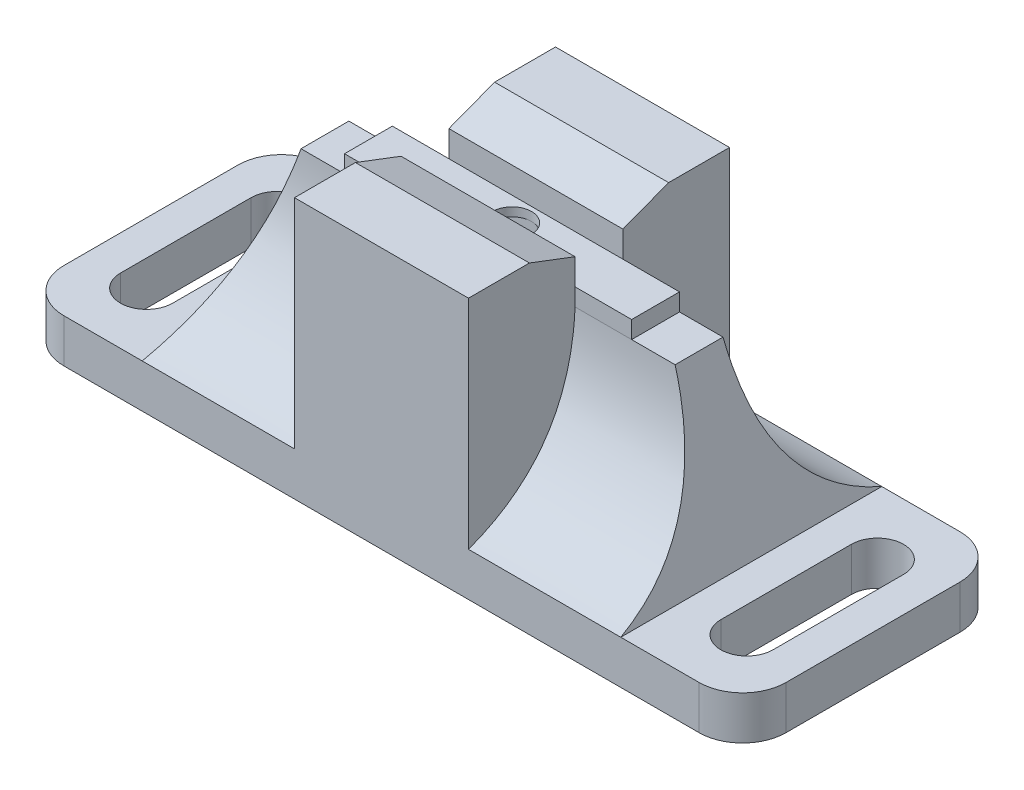
SolidWorks part; units mm, degrees
ref_plane "Front Plane" through (0, 0, 0) normal (0, 0, 1) x (1, 0, 0)
ref_plane "Top Plane" through (0, 0, 0) normal (0, 1, 0) x (1, 0, 0)
ref_plane "Right Plane" through (0, 0, 0) normal (1, 0, 0) x (0, 0, -1)
sketch "Sketch1" plane through (0, 0, 0) normal (0, 1, 0) x (1, 0, 0)
  line L0 (-34.5, 7.5) -> (-34.5, -7.5) construction
  line L1 (-36.5, 15) -> (36.5, 15)
  line L2 (-41.5, 10) -> (-41.5, -10)
  line L3 (-36.5, -15) -> (36.5, -15)
  line L4 (41.5, 10) -> (41.5, -10)
  line L5 (0, -15) -> (0, 15) construction
  line L6 (-41.5, 0) -> (41.5, 0) construction
  line L7 (-31.5, 7.5) -> (-31.5, -7.5)
  line L8 (-37.5, 7.5) -> (-37.5, -7.5)
  line L9 (34.5, 7.5) -> (34.5, -7.5) construction
  line L10 (31.5, 7.5) -> (31.5, -7.5)
  line L11 (37.5, 7.5) -> (37.5, -7.5)
  arc A0 (36.5, 15) -> (41.5, 10) centre (36.5, 10) cw
  arc A1 (36.5, -15) -> (41.5, -10) centre (36.5, -10) ccw
  arc A2 (-41.5, -10) -> (-36.5, -15) centre (-36.5, -10) ccw
  arc A3 (-36.5, 15) -> (-41.5, 10) centre (-36.5, 10) ccw
  arc A4 (-31.5, 7.5) -> (-37.5, 7.5) centre (-34.5, 7.5) ccw
  arc A5 (-37.5, -7.5) -> (-31.5, -7.5) centre (-34.5, -7.5) ccw
  arc A6 (31.5, 7.5) -> (37.5, 7.5) centre (34.5, 7.5) cw
  arc A7 (37.5, -7.5) -> (31.5, -7.5) centre (34.5, -7.5) cw
  point P0 (0, 0)
  point P6 (41.5, 15)
  point P14 (-41.5, -15)
  point P17 (-41.5, 15)
  point P20 (-34.5, 0)
  point P25 (0, 0)
  point P28 (34.5, 0)
  dimension "D3" = 5
  dimension "D1" = 30
  dimension "D2" = 83
  dimension "D4" = 6
  dimension "D5" = 4
  dimension "D6" = 15
extrude "Boss-Extrude1" add sketch "Sketch1" against normal blind 5
sketch "Sketch2" plane through (0, 0, 0) normal (1, 0, 0) x (0, 0, -1)
  line L0 (0, 0) -> (0, 18) construction
  line L1 (-2.75, 18) -> (2.75, 18)
  line L2 (-15, 0) -> (-15, 25)
  line L3 (-15, 25) -> (-8, 25)
  line L5 (-2.75, 18) -> (-2.75, 23)
  line L6 (-2.75, 23) -> (-8, 25)
  line L7 (2.75, 18) -> (2.75, 23)
  line L8 (2.75, 23) -> (8, 25)
  line L9 (15, 25) -> (8, 25)
  line L10 (15, 0) -> (15, 25)
  line L11 (-15, 0) -> (15, 0)
  spline S0 degree 2 poles (-15, 0) (-3.3423, 4.2875) (-2.75, 18) knots 0 0 0 1 1 1
  spline S1 degree 2 poles (15, 0) (3.3423, 4.2875) (2.75, 18) knots 0 0 0 1 1 1
  point P5 (0, 18)
  dimension "D1" = 18
  dimension "D2" = 5.5
  dimension "D3" = 25
  dimension "D4" = 5
  dimension "D5" = 7
extrude "Boss-Extrude2" add sketch "Sketch2" along normal mid plane 55 contours L11 L0 L1 S0 | L0 L11 S1 L1 region at (0, 6.3784, 3.8586) region at (0, 6.3784, -3.8586)
extrude "Boss-Extrude3" add sketch "Sketch2<3>" along normal mid plane 20 contours L2 S0 L5 L6 L3 | S1 L10 L9 L8 L7 region at (0, 14.2334, 9.6564) region at (0, 14.2334, -9.6564)
sketch "Sketch2<3>" plane through (0, 0, 0) normal (1, 0, 0) x (0, 0, -1) same geometry as "Sketch2"
sketch "Sketch5" plane through (0, 0, 0) normal (0, 0, 1) x (1, 0, 0)
  line L0 (10, 0) -> (10, 18) construction
  line L1 (27.5, 0) -> (27.5, 18) construction
  line L2 (27.5, 18) -> (10, 18) construction
  line L3 (-27.5, 0) -> (-36.5, 0) construction
  line L4 (-36.5, 0) -> (-36.5, -5) construction
  line L5 (-36.5, -5) -> (36.5, -5) construction
  line L6 (36.5, -5) -> (36.5, 0) construction
  line L7 (36.5, 0) -> (27.5, 0) construction
  line L8 (10, 0) -> (10, 25) construction
  line L9 (10, 25) -> (-10, 25) construction
  line L10 (-10, 25) -> (-10, 0) construction
  line L11 (-10, 18) -> (-10, 0) construction
  line L12 (-10, 18) -> (-27.5, 18) construction
  line L13 (-27.5, 18) -> (-27.5, 0) construction
  line L14 (10, 0) -> (10, 18)
  line L15 (27.5, 0) -> (27.5, 18)
  line L16 (27.5, 18) -> (10, 18)
  line L17 (-27.5, 0) -> (-36.5, 0)
  line L18 (-36.5, 0) -> (-36.5, -5)
  line L19 (-36.5, -5) -> (36.5, -5)
  line L20 (36.5, -5) -> (36.5, 0)
  line L21 (36.5, 0) -> (27.5, 0)
  line L22 (10, 0) -> (10, 25)
  line L23 (10, 25) -> (-10, 25)
  line L24 (-10, 25) -> (-10, 0)
  line L25 (-10, 18) -> (-10, 0)
  line L26 (-10, 18) -> (-27.5, 18)
  line L27 (-27.5, 18) -> (-27.5, 0)
  line L28 (-27.5, 0) -> (-21.5, 18)
  line L29 (27.5, 0) -> (21.5, 18)
  line L30 (-21.5, 18) -> (21.5, 18)
  line L31 (0, 0) -> (0, 18) construction
  line L32 (-21.5, 18) -> (-16.5, 18)
  line L33 (-21.5, 18) -> (-21.5, 16)
  line L34 (-21.5, 16) -> (-16.5, 16)
  line L35 (-16.5, 18) -> (-16.5, 16)
  line L36 (21.5, 18) -> (21.5, 16)
  line L37 (21.5, 16) -> (16.5, 16)
  line L38 (16.5, 18) -> (16.5, 16)
  line L40 (-16.5, 18) -> (16.5, 18)
  line L41 (-16.5, 18) -> (-16.5, 20)
  line L42 (-16.5, 20) -> (16.5, 20)
  line L43 (16.5, 18) -> (16.5, 20)
  point P18 (0, 18)
  point P30 (0, 0)
  dimension "D1" = 43
  dimension "D2" = 5
  dimension "D3" = 2
  dimension "D4" = 2
extrude "Cut-Extrude2" cut sketch "Sketch5" against normal through all both and the other way through all contours L27 L28 L26 | L29 L15 L16 region at (25.5, 12, 0) region at (-25.5, 12, 0)
extrude "Boss-Extrude4" add sketch "Sketch5<3>" along normal mid plane 5.5 contours L30 L43 L42 L22 | L42 L41 L26 L24 | L42 L24 L30 L40 L22 region at (13.25, 19, 0) region at (0, 19, 0) region at (-13.25, 19, 0)
sketch "Sketch5<3>" plane through (0, 0, 0) normal (0, 0, 1) x (1, 0, 0) same geometry as "Sketch5"
sketch "Sketch6" plane through (0, -5, 0) normal (0, -1, 0) x (1, 0, 0)
  line L0 (-10, 2.25) -> (-16, 2.25)
  line L1 (-16, 2.25) -> (-16, -2.25)
  line L2 (-16, -2.25) -> (-10, -2.25)
  line L3 (-10, -2.25) -> (10, -2.25)
  line L4 (10, -2.25) -> (16, -2.25)
  line L5 (16, -2.25) -> (16, 2.25)
  line L6 (16, 2.25) -> (10, 2.25)
  line L7 (10, 2.25) -> (-10, 2.25)
  line L8 (-16.5, -2.75) -> (-10, -2.75)
  line L9 (-16.5, 2.75) -> (-16.5, -2.75)
  line L10 (-10, 2.75) -> (-16.5, 2.75)
  line L11 (10, 2.75) -> (-10, 2.75)
  line L12 (16.5, 2.75) -> (10, 2.75)
  line L13 (16.5, -2.75) -> (16.5, 2.75)
  line L14 (10, -2.75) -> (16.5, -2.75)
  line L15 (-10, -2.75) -> (10, -2.75)
  line L16 (-16.5, -2.75) -> (-10, -2.75)
  line L17 (-16.5, 2.75) -> (-16.5, -2.75)
  line L18 (-10, 2.75) -> (-16.5, 2.75)
  line L19 (10, 2.75) -> (-10, 2.75)
  line L20 (16.5, 2.75) -> (10, 2.75)
  line L21 (16.5, -2.75) -> (16.5, 2.75)
  line L22 (10, -2.75) -> (16.5, -2.75)
  line L23 (-10, -2.75) -> (10, -2.75)
  dimension "D1" = 0
  dimension "D2" = 0.5
extrude "Cut-Extrude3" cut sketch "Sketch6" against normal offset from surface 1 and the other way through all contours L6 L7 L0 L1 L2 L3 L4 L5 region at (0, -5, 0) up to face at (0, 20, 0)
hole_wizard "M4 Clearance Hole1" positions "Sketch7" profile "Sketch8" hole size "M4" standard "ISO" end condition through all
sketch "Sketch7" plane through (0, 20, 0) normal (0, 1, 0) x (1, 0, 0)
  point P0 (0, 0)
sketch "Sketch8" plane through (0, 20, 0) normal (1, 0, 0) x (0, 0, 1)
  line L0 (0, 0) -> (0, 25)
  line L1 (0, 25) -> (2.25, 25)
  line L2 (2.25, 25) -> (2.25, 0)
  line L5 (2.25, 0) -> (0, 0)
  line L11 (0, -6.35) -> (0, 107.95) construction
  dimension "Thru Hole Dia." = 4.5
  dimension "Thru Hole Depth" = 25
